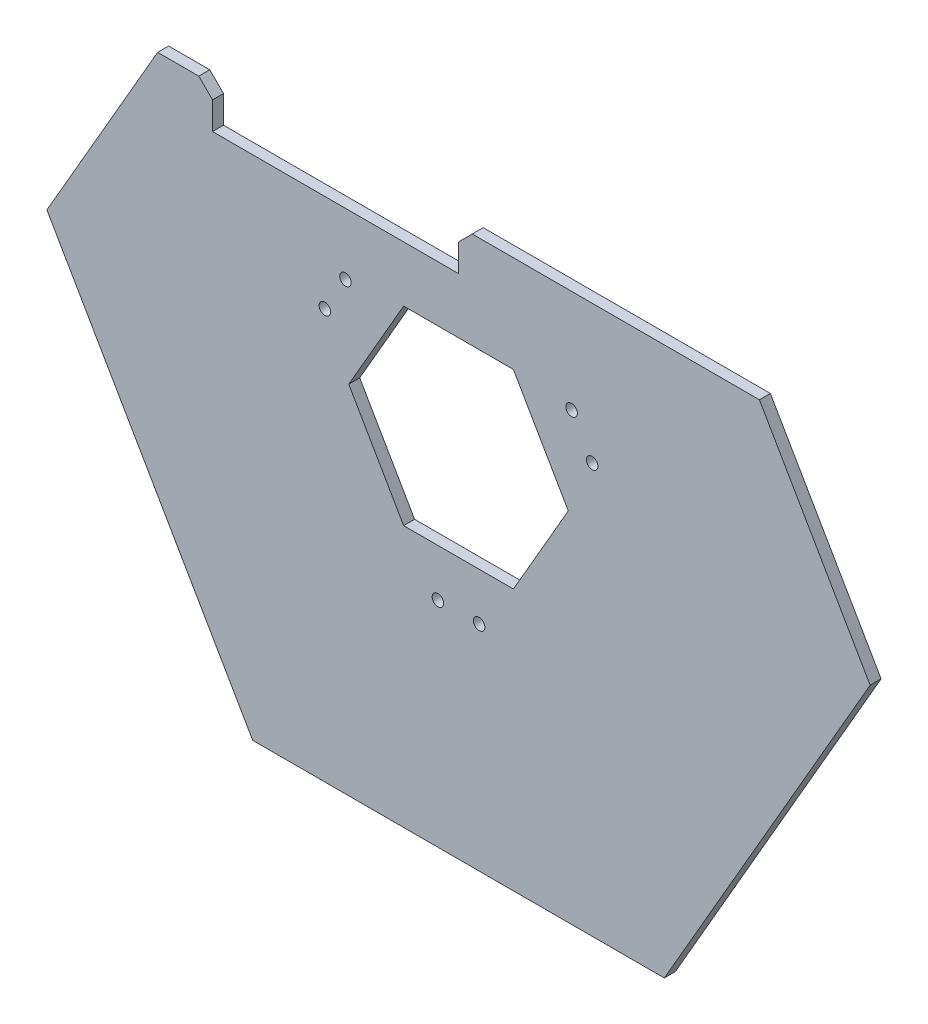
SolidWorks part; units mm, degrees
material "5052-O"
ref_plane "前基準面" through (0, 0, 0) normal (0, 0, 1) x (1, 0, 0)
ref_plane "上基準面" through (0, 0, 0) normal (0, 1, 0) x (1, 0, 0)
ref_plane "右基準面" through (0, 0, 0) normal (1, 0, 0) x (0, 0, -1)
sketch "草圖1" plane through (0, 0, 0) normal (0, 0, 1) x (1, 0, 0)
  line L1 (150, 0) -> (75, 129.9038)
  line L2 (75, 129.9038) -> (-75, 129.9038)
  line L3 (-75, 129.9038) -> (-150, 0)
  line L4 (-150, 0) -> (-75, -129.9038)
  line L5 (-75, -129.9038) -> (75, -129.9038)
  line L6 (75, -129.9038) -> (150, 0)
  circle A0 centre (0, 0) radius 129.9038 construction
  dimension "D1" = 150
extrude "填料-伸長1" add sketch "草圖1" along normal blind 4
ref_axis "基準軸1" through (0, 0, 0) along (0, 0, 1)
sketch "草圖2" plane through (0, 0, 4) normal (0, 0, 1) x (1, 0, 0)
  line L0 (-7.5, -51.9038) -> (7.5, -51.9038) construction
  line L1 (-75, -129.9038) -> (75, -129.9038) construction
  circle A0 centre (-7.5, -51.9038) radius 2.1
  circle A1 centre (7.5, -51.9038) radius 2.1
  point P4 (0, -51.9038)
  dimension "D1" = 4.2
  dimension "D2" = 4.2
  dimension "D3" = 78
  dimension "D4" = 15
extrude "除料-伸長1" cut sketch "草圖2" against normal up to next
sketch "草圖3" plane through (0, 0, 4) normal (0, 0, 1) x (1, 0, 0)
  line L0 (-109.641, 69.9038) -> (-89.641, 69.9038)
  line L1 (-75, 129.9038) -> (-150, 0) construction
  line L2 (-89.641, 69.9038) -> (-89.641, 54.9038)
  line L3 (-89.641, 54.9038) -> (0, 54.9038)
  line L4 (0, 54.9038) -> (0, 69.9038)
  line L5 (0, 69.9038) -> (109.641, 69.9038)
  line L6 (150, 0) -> (75, 129.9038) construction
  line L7 (75, 129.9038) -> (-75, 129.9038) construction
  point P16 (0, 129.9038)
  dimension "D1" = 75
  dimension "D2" = 15
  dimension "D4" = 20
extrude "除料-伸長2" cut sketch "草圖3" against normal blind 4 and the other way through all
sketch "草圖4" plane through (0, 0, 4) normal (0, 0, 1) x (1, 0, 0)
  line L1 (40, 0) -> (20, 34.641)
  line L2 (20, 34.641) -> (-20, 34.641)
  line L3 (-20, 34.641) -> (-40, 0)
  line L4 (-40, 0) -> (-20, -34.641)
  line L5 (-20, -34.641) -> (20, -34.641)
  line L6 (20, -34.641) -> (40, 0)
  circle A0 centre (0, 0) radius 34.641 construction
  dimension "D1" = 40
extrude "除料-伸長3" cut sketch "草圖4" against normal up to next
pattern_circular "環狀複製排列1" count 3 over 360 about axis through (0, 0, 0) along (0, 0, 1) of "除料-伸長1"
chamfer "導角1" distance 5 angle 45 2 edges at (0, 69.9038, 2) (-89.641, 69.9038, 2)
